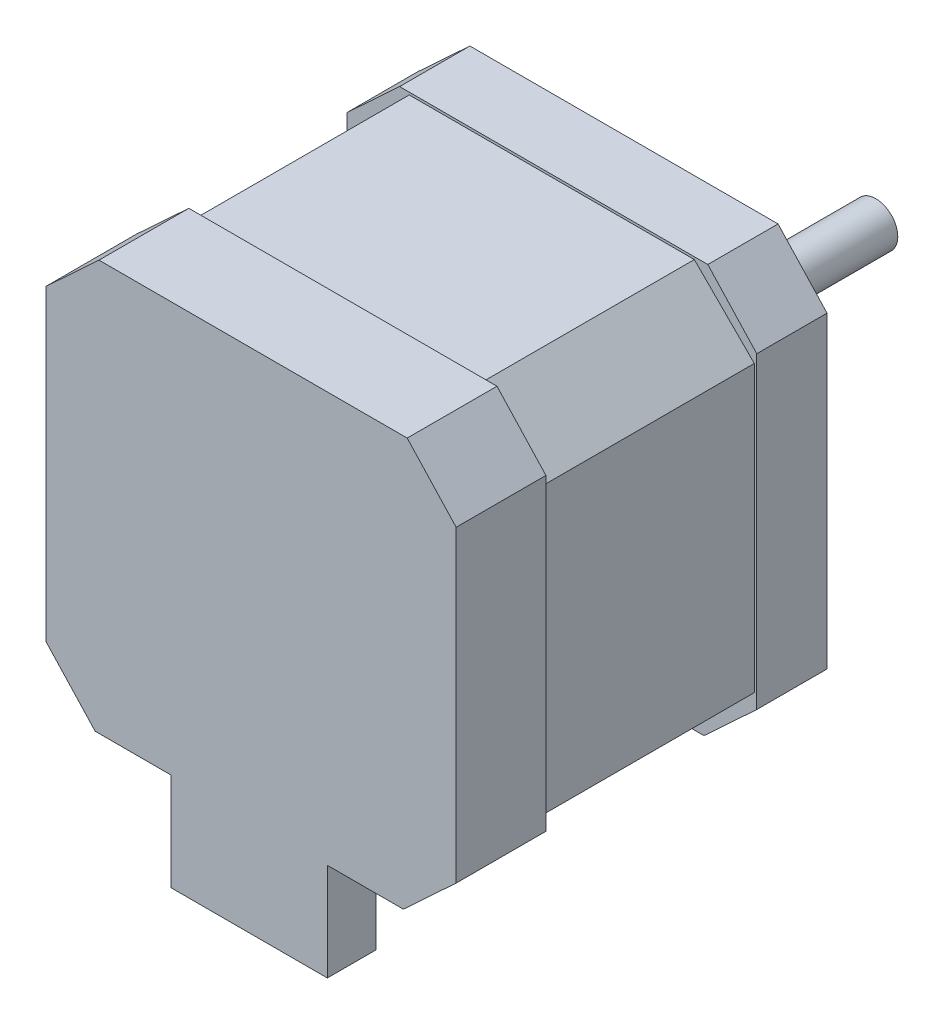
SolidWorks part; units mm, degrees
material "Ferro dúctil"
ref_plane "Plano frontal" through (0, 0, 0) normal (0, 0, 1) x (1, 0, 0)
ref_plane "Plano superior" through (0, 0, 0) normal (0, 1, 0) x (1, 0, 0)
ref_plane "Plano direito" through (0, 0, 0) normal (1, 0, 0) x (0, 0, -1)
sketch "Esboço1" plane through (0, 0, 0) normal (0, 0, 1) x (1, 0, 0)
  line L0 (-1.3818, -36.7436) -> (-36.7436, 1.3818)
  line L1 (-21, 21) -> (21, 21)
  line L2 (-21, 21) -> (-21, -21)
  line L3 (-21, -21) -> (21, -21)
  line L4 (21, 21) -> (21, -21)
  line L5 (-21, 21) -> (21, -21) construction
  line L6 (-21, -21) -> (21, 21) construction
  line L7 (-1.3818, -36.7436) -> (36.7436, -1.3818)
  line L8 (-36.7436, 1.3818) -> (1.3818, 36.7436)
  line L9 (36.7436, -1.3818) -> (1.3818, 36.7436)
  line L10 (-1.3818, -36.7436) -> (1.3818, 36.7436) construction
  line L11 (-36.7436, 1.3818) -> (36.7436, -1.3818) construction
  point P0 (0, 0)
  point P7 (0, 0)
  dimension "D1" = 42
  dimension "D2" = 52
extrude "Ressalto-extrusão1" add sketch "Esboço1" along normal blind 38 contours L4 L9 L1 L8 L2 L0 L3 L7 region at (0, 0, 0)
sketch "Esboço2" plane through (0, 0, 38) normal (0, 0, 1) x (1, 0, 0)
  line L1 (-20.75, -20.75) -> (20.75, -20.75)
  line L2 (-20.75, -20.75) -> (-20.75, 20.75)
  line L3 (-20.75, 20.75) -> (20.75, 20.75)
  line L4 (20.75, -20.75) -> (20.75, 20.75)
  line L5 (-20.75, -20.75) -> (20.75, 20.75) construction
  line L6 (-20.75, 20.75) -> (20.75, -20.75) construction
  line L7 (0, -35.3553) -> (-35.3553, 0)
  line L8 (0, -35.3553) -> (35.3553, 0)
  line L9 (-35.3553, 0) -> (0, 35.3553)
  line L10 (35.3553, 0) -> (0, 35.3553)
  line L11 (0, -35.3553) -> (0, 35.3553) construction
  line L12 (-35.3553, 0) -> (35.3553, 0) construction
  point P0 (0, 0)
  point P8 (-17.6777, 17.6777)
  point P9 (0, 0)
  dimension "D1" = 50
  dimension "D2" = 41.5
extrude "Corte-Extrusão-Fina1" cut sketch "Esboço2" against normal offset from surface (21.6 mm away) 7.2 from offset 9.2 thin contours L4 L10 L3 L9 L2 L7 L1 L8 up to face at (0, 0, 0) offset against normal yes thin type one direction wall 10
sketch "Esboço3" plane through (0, 0, 0) normal (0, 0, -1) x (-1, 0, 0)
  circle A0 centre (0, 0) radius 2.25
  dimension "D1" = 4.5
extrude "Ressalto-extrusão2" add sketch "Esboço3" along normal blind 26
sketch "Esboço4" plane through (0, 0, 0) normal (0, 0, -1) x (-1, 0, 0)
  circle A0 centre (0, 0) radius 10
  dimension "D1" = 20
extrude "Ressalto-extrusão3" add sketch "Esboço4" along normal blind 2
sketch "Esboço5" plane through (0, 0, 0) normal (0, 0, -1) x (-1, 0, 0)
  line L1 (15.5, 15.5) -> (-15.5, 15.5) construction
  line L2 (15.5, 15.5) -> (15.5, -15.5) construction
  line L3 (15.5, -15.5) -> (-15.5, -15.5) construction
  line L4 (-15.5, 15.5) -> (-15.5, -15.5) construction
  line L5 (15.5, 15.5) -> (-15.5, -15.5) construction
  line L6 (15.5, -15.5) -> (-15.5, 15.5) construction
  circle A0 centre (15.5, -15.5) radius 1.5
  circle A1 centre (-15.5, -15.5) radius 1.5
  circle A2 centre (-15.5, 15.5) radius 1.5
  circle A3 centre (15.5, 15.5) radius 1.5
  point P0 (0, 0)
  dimension "D1" = 3
  dimension "D2" = 31
extrude "Corte-extrusão1" cut sketch "Esboço5" against normal blind 10
sketch "Esboço7" plane through (0, -21, 0) normal (0, -1, 0) x (1, 0, 0)
  line L0 (-15.9842, 38) -> (15.5922, 38) construction
  line L1 (7.804, 33) -> (-8.196, 33)
  line L2 (7.804, 33) -> (7.804, 38)
  line L3 (7.804, 38) -> (-8.196, 38)
  line L4 (-8.196, 33) -> (-8.196, 38)
  line L5 (7.804, 33) -> (-8.196, 38) construction
  line L6 (7.804, 38) -> (-8.196, 33) construction
  line L7 (-15.9842, 0) -> (15.5922, 0) construction
  point P0 (-0.196, 35.5)
  point P10 (-0.196, 0)
  dimension "D1" = 5
  dimension "D2" = 16
extrude "Ressalto-extrusão4" add sketch "Esboço7" along normal blind 10
